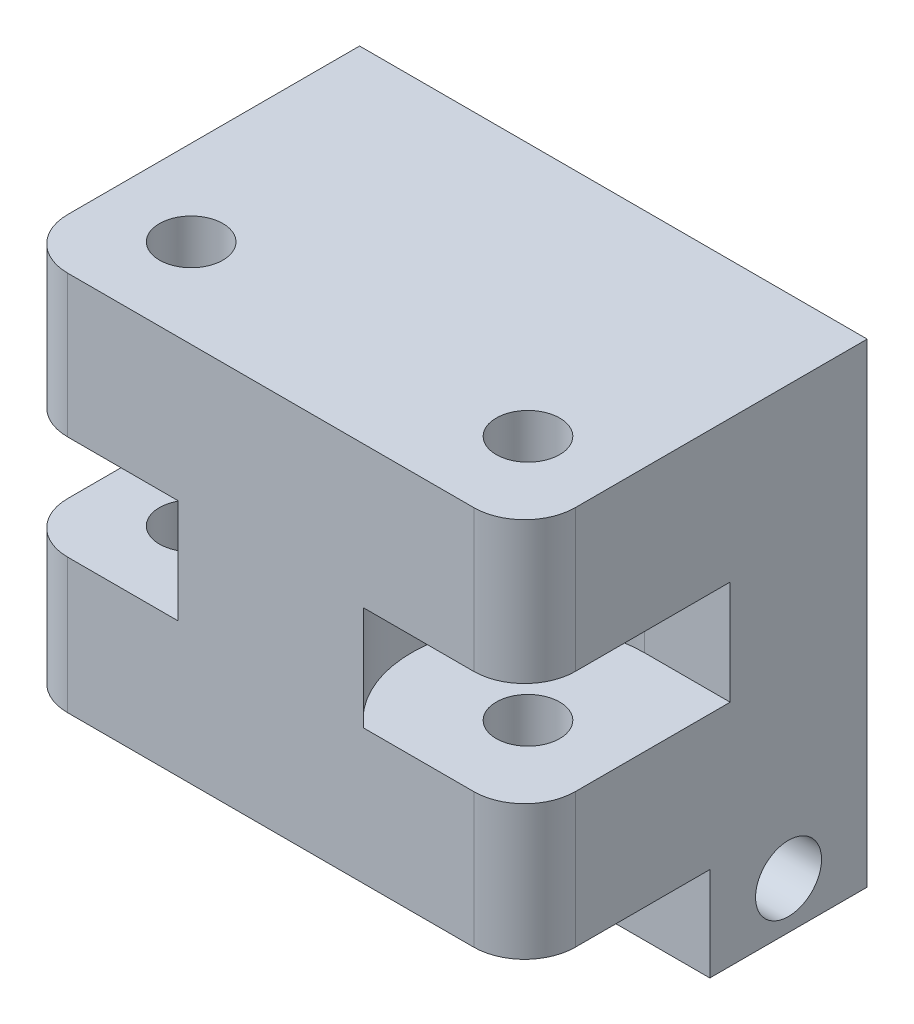
SolidWorks part; units mm, degrees
ref_plane "Front Plane" through (0, 0, 0) normal (0, 0, 1) x (1, 0, 0)
ref_plane "Top Plane" through (0, 0, 0) normal (0, 1, 0) x (1, 0, 0)
ref_plane "Right Plane" through (0, 0, 0) normal (1, 0, 0) x (0, 0, -1)
sketch "Sketch1" plane through (0, 0, 0) normal (0, 1, 0) x (1, 0, 0)
  line L1 (-22.8462, -9.1868) -> (17.1538, -9.1868)
  line L2 (-22.8462, -9.1868) -> (-22.8462, 17.8132)
  line L3 (-22.8462, 17.8132) -> (17.1538, 17.8132)
  line L4 (17.1538, -9.1868) -> (17.1538, 17.8132)
  dimension "D1" = 27
  dimension "D2" = 40
extrude "Boss-Extrude1" add sketch "Sketch1" along normal blind 30
sketch "Sketch2" plane through (0, 0, -17.8132) normal (0, 0, -1) x (-1, 0, 0)
  line L0 (2.8462, 30) -> (2.8462, 0) construction
  line L1 (-8.0864, 4) -> (-0.2064, 4)
  line L2 (-0.2064, 4) -> (-0.2064, 7)
  line L3 (-0.2064, 7) -> (-2.8664, 7)
  line L4 (-2.8664, 7) -> (-2.8664, 8.0087)
  line L5 (-2.8664, 8.0087) -> (-0.2538, 10.6287)
  line L6 (-0.2538, 10.6287) -> (5.9462, 10.6287)
  line L7 (-17.1538, 30) -> (22.8462, 30) construction
  line L8 (-17.1538, 0) -> (22.8462, 0) construction
  line L9 (-8.0864, 4) -> (-8.0864, 26)
  line L10 (-8.0864, 26) -> (-0.2064, 26)
  line L11 (-0.2064, 26) -> (-0.2064, 23)
  line L12 (-0.2064, 23) -> (-2.8664, 23)
  line L13 (-2.8664, 23) -> (-2.8664, 21.9913)
  line L14 (-2.8664, 21.9913) -> (-0.2464, 19.3787)
  line L15 (-0.2464, 19.3787) -> (5.9536, 19.3787)
  line L16 (-17.1538, 15) -> (22.8462, 15) construction
  line L17 (-17.1538, 30) -> (-17.1538, 0) construction
  line L18 (22.8462, 30) -> (22.8462, 0) construction
  line L19 (5.9387, 19.3787) -> (-0.2613, 19.3787)
  line L20 (8.5587, 21.9913) -> (5.9387, 19.3787)
  line L21 (8.5587, 23) -> (8.5587, 21.9913)
  line L22 (5.8987, 23) -> (8.5587, 23)
  line L23 (5.8987, 26) -> (5.8987, 23)
  line L24 (13.7787, 26) -> (5.8987, 26)
  line L25 (13.7787, 4) -> (13.7787, 26)
  line L26 (8.5587, 8.0087) -> (5.9462, 10.6287)
  line L27 (8.5587, 7) -> (8.5587, 8.0087)
  line L28 (5.8987, 7) -> (8.5587, 7)
  line L29 (5.8987, 4) -> (5.8987, 7)
  line L30 (13.7787, 4) -> (5.8987, 4)
  point P26 (-8.0864, 15)
  point P27 (2.8462, 15)
  point P37 (2.8462, 10.6287)
  dimension "D1" = 6.2
  dimension "D2" = 2.62
  dimension "D3" = 3.7
  dimension "D4" = 8.75
  dimension "D5" = 7.88
  dimension "D6" = 22
  dimension "D7" = 5.22
  dimension "D8" = 3
  dimension "D9" = 90
extrude "Cut-Extrude1" cut sketch "Sketch2" against normal blind 10 contours L30 L25 L24 L23 L22 L21 L20 L15 L14 L13 L12 L11 L10 L9 L1 L2 L3 L4 L5 L6 L26 L27 L28 L29 region at (-2.8462, 15.0011, -17.8132)
sketch "Sketch3" plane through (0, 0, 0) normal (0, -1, 0) x (1, 0, 0)
  line L0 (-22.8462, 9.1868) -> (17.1538, 9.1868) construction
  line L1 (17.1538, 9.1868) -> (17.1538, -17.8132) construction
  line L2 (-2.8462, 9.1868) -> (-2.8462, -17.8132) construction
  line L3 (17.1538, -17.8132) -> (-22.8462, -17.8132) construction
  circle A0 centre (10.4238, 2.1868) radius 2.5
  circle A2 centre (-16.1162, 2.1868) radius 2.5
  dimension "D1" = 5
  dimension "D3" = 7
  dimension "D4" = 6.73
extrude "Cut-Extrude2" cut sketch "Sketch3" against normal blind 30
sketch "Sketch8" plane through (0, 0, 0) normal (0, -1, 0) x (1, 0, 0)
  line L0 (4.4539, 9.1868) -> (17.1538, 9.1868)
  line L1 (-22.8462, 9.1868) -> (17.1538, 9.1868) construction
  line L2 (17.1538, 9.1868) -> (17.1538, -7.0132)
  line L3 (17.1538, 9.1868) -> (17.1538, -17.8132) construction
  line L4 (17.1538, -7.0132) -> (10.4238, -7.0132)
  line L6 (-2.8462, -17.8132) -> (-2.8462, 9.1868) construction
  line L7 (17.1538, -17.8132) -> (-22.8462, -17.8132) construction
  line L8 (-22.8462, -7.0132) -> (-16.1162, -7.0132)
  line L9 (-22.8462, 9.1868) -> (-22.8462, -7.0132)
  line L10 (-10.1462, 9.1868) -> (-22.8462, 9.1868)
  arc A0 (10.4238, -7.0132) -> (4.4539, 9.1868) centre (10.4238, 2.1868) cw
  arc A1 (-16.1162, -7.0132) -> (-10.1462, 9.1868) centre (-16.1162, 2.1868) ccw
  circle M6 centre (10.4238, 2.1868) radius 2.5
  circle M7 centre (-16.1162, 2.1868) radius 2.5
  line M8 (-22.8462, 9.1868) -> (-22.8462, -17.8132)
  line M10 (17.1538, -17.8132) -> (17.1538, 9.1868)
  line M11 (17.1538, 9.1868) -> (-22.8462, 9.1868)
  dimension "D1" = 9.2
  dimension "D2" = 6.73
extrude "Cut-Extrude5" cut sketch "Sketch8" against normal blind 8.2 from offset 10.62 contours A0 L4 M10 M11 M6 | M6 | L8 A1 M11 M8 M7 | M7 region at (10.8039, 0, 8.9596) region at (-7.6968, 0, -0.9158) region at (10.4238, 0, 2.1868) region at (-16.1162, 0, 2.1868) offset against normal yes
sketch "Sketch10" plane through (8.0864, 0, 0) normal (-1, 0, 0) x (0, 0, 1)
  line L0 (-17.8132, 30) -> (-17.8132, 0) construction
  line L1 (-17.8132, 18.82) -> (2.1868, 18.82)
  line L2 (-17.8132, 18.82) -> (-17.8132, 10.62)
  line L3 (-17.8132, 10.62) -> (2.1868, 10.62)
  line L4 (2.1868, 18.82) -> (2.1868, 10.62)
  line L5 (-17.8132, 30) -> (9.1868, 30) construction
  dimension "D1" = 20
  dimension "D2" = 11.18
  dimension "D3" = 8.2
extrude "Cut-Extrude7" cut sketch "Sketch10" along normal blind 6.8
sketch "Sketch12" plane through (-13.7787, 0, 0) normal (1, 0, 0) x (0, 0, -1)
  line L1 (17.8132, 18.82) -> (-2.1868, 18.82)
  line L2 (17.8132, 18.82) -> (17.8132, 10.62)
  line L3 (17.8132, 10.62) -> (-2.1868, 10.62)
  line L4 (-2.1868, 18.82) -> (-2.1868, 10.62)
  line L5 (-9.1868, 30) -> (17.8132, 30) construction
  dimension "D1" = 20
  dimension "D2" = 8.2
  dimension "D3" = 11.18
extrude "Cut-Extrude10" cut sketch "Sketch12" along normal blind 6.8
fillet "Fillet1" radius 4 4 edges at (17.1538, 5.31, 9.1868) (17.1538, 24.41, 9.1868) (-22.8462, 5.31, 9.1868) (-22.8462, 24.41, 9.1868)
sketch "Sketch13" plane through (17.1538, 0, 0) normal (1, 0, 0) x (0, 0, -1)
  line L0 (-5.1868, 0) -> (17.8132, 0) construction
  line L1 (17.8132, 30) -> (17.8132, 0) construction
  line L3 (17.8132, 0) -> (5.4132, 0)
  line L4 (17.8132, 0) -> (17.8132, -7.4)
  line L5 (17.8132, -7.4) -> (5.4132, -7.4)
  line L6 (5.4132, 0) -> (5.4132, -7.4)
  circle A0 centre (11.6132, -3.7) radius 2.6
  dimension "D1" = 6.2
  dimension "D2" = 3.7
  dimension "D3" = 5.2
  dimension "D4" = 12.4
  dimension "D5" = 7.4
extrude "Boss-Extrude2" add sketch "Sketch13" against normal up to surface (40 mm away) up to face at (-22.8462, 14.86, -3.6132)
